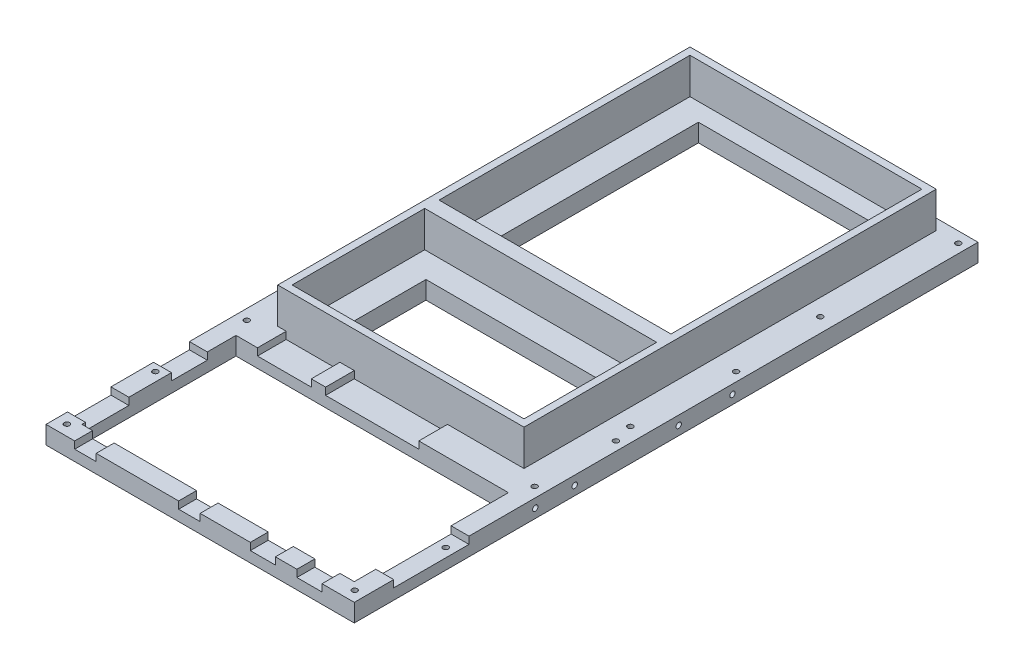
SolidWorks part; units mm, degrees
ref_plane "前视基准面" through (0, 0, 0) normal (0, 0, 1) x (1, 0, 0)
ref_plane "上视基准面" through (0, 0, 0) normal (0, 1, 0) x (1, 0, 0)
ref_plane "右视基准面" through (0, 0, 0) normal (1, 0, 0) x (0, 0, -1)
other "Configuration Table"
sketch "草图1" plane through (0, 0, 0) normal (0, 1, 0) x (1, 0, 0)
  line L1 (-43, -60.5) -> (43, -60.5)
  line L2 (-43, -60.5) -> (-43, 60.5)
  line L3 (-43, 60.5) -> (43, 60.5)
  line L4 (43, -60.5) -> (43, 60.5)
  line L5 (-43, -60.5) -> (43, 60.5) construction
  line L6 (-43, 60.5) -> (43, -60.5) construction
  line L7 (-25, 50.5) -> (25, 50.5)
  line L8 (-25, 50.5) -> (-25, -4.5)
  line L9 (-25, -4.5) -> (25, -4.5)
  line L10 (25, 50.5) -> (25, -4.5)
  line L11 (-25, -25.5) -> (25, -25.5)
  line L12 (-25, -25.5) -> (-25, -50.5)
  line L13 (-25, -50.5) -> (25, -50.5)
  line L14 (25, -25.5) -> (25, -50.5)
  line L15 (-43, -60.5) -> (43, -60.5)
  line L16 (-43, -60.5) -> (-43, -113.5)
  line L17 (-43, -113.5) -> (43, -113.5)
  line L18 (43, -60.5) -> (43, -113.5)
  line L19 (-38, -65.5) -> (38, -65.5)
  line L20 (-38, -65.5) -> (-38, -108.5)
  line L21 (-38, -108.5) -> (38, -108.5)
  line L22 (38, -65.5) -> (38, -108.5)
  point P0 (0, 0)
  dimension "D1" = 86
  dimension "D2" = 121
  dimension "D3" = 10
  dimension "D4" = 18
  dimension "D5" = 18
  dimension "D6" = 55
  dimension "D7" = 10
  dimension "D8" = 25
  dimension "D9" = 5
  dimension "D10" = 5
  dimension "D11" = 5
  dimension "D12" = 5
  dimension "D13" = 53
extrude "凸台-拉伸1" add sketch "草图1" along normal blind 5 contours L18 L1 L16 L17 L19 L22 L21 L20 | L2 L3 L4 L1 | L9 L10 L7 L8 | L11 L14 L13 L12 region at (0, 0, 61.5102)
sketch "草图4" plane through (0, 5, 0) normal (0, 1, 0) x (1, 0, 0)
  line L0 (-43, 60.5) -> (43, 60.5) construction
  line L1 (-34.35, 57.5) -> (34.35, 57.5)
  line L2 (-34.35, 57.5) -> (-34.35, -57.5)
  line L3 (-34.35, -57.5) -> (34.35, -57.5)
  line L4 (34.35, 57.5) -> (34.35, -57.5)
  line L5 (-32.35, -18.5) -> (32.35, -18.5)
  line L6 (-32.35, -18.5) -> (-32.35, -55.5)
  line L7 (-32.35, -55.5) -> (32.35, -55.5)
  line L8 (32.35, -18.5) -> (32.35, -55.5)
  line L9 (32.35, -14.5) -> (-32.35, -14.5)
  line L10 (32.35, -14.5) -> (32.35, 55.5)
  line L11 (32.35, 55.5) -> (-32.35, 55.5)
  line L12 (-32.35, -14.5) -> (-32.35, 55.5)
  line L13 (43, 60.5) -> (43, -113.5) construction
  line L14 (-43, 60.5) -> (-43, -113.5) construction
  dimension "D1" = 5
  dimension "D2" = 10.65
  dimension "D3" = 10.65
  dimension "D4" = 2
  dimension "D5" = 2
  dimension "D6" = 2
  dimension "D7" = 70
  dimension "D8" = 79
  dimension "D9" = 37
  dimension "D10" = 2
extrude "凸台-拉伸2" add sketch "草图4" along normal blind 10 contours L3 L4 L1 L2 | L6 L7 L8 L5 | L12 L11 L10 L9
sketch "草图5" plane through (0, 5, 0) normal (0, 1, 0) x (1, 0, 0)
  line L0 (-43, 60.5) -> (-43, -113.5) construction
  line L1 (43, 60.5) -> (43, -113.5) construction
  line L2 (-43, 60.5) -> (43, 60.5) construction
  line L3 (-43, -85.5) -> (-38, -85.5)
  line L4 (-38, -65.5) -> (-38, -108.5) construction
  line L5 (-23.6333, -57.5) -> (-23.6333, -113.5)
  line L6 (-34.35, -57.5) -> (34.35, -57.5) construction
  line L7 (-43, -113.5) -> (43, -113.5) construction
  line L8 (38, -85.5) -> (43, -85.5)
  line L9 (38, -65.5) -> (38, -108.5) construction
  line L10 (-25, -25.5) -> (-25, -50.5) construction
  line L12 (-34.35, 57.5) -> (34.35, 57.5) construction
  line L13 (-25, -4.5) -> (25, -4.5) construction
  circle A0 centre (-39, 20.5) radius 0.75
  circle A1 centre (39, 20.5) radius 0.75
  circle A2 centre (-39, -32.5) radius 0.75
  circle A3 centre (39, -32.5) radius 0.75
  circle A4 centre (-40.1428, -60.35) radius 0.75
  circle A5 centre (40.1428, -60.35) radius 0.75
  circle A6 centre (-40.1428, -110.5303) radius 0.75
  circle A7 centre (40.1428, -110.5303) radius 0.75
  circle A8 centre (-40.5, 57.5) radius 0.75
  circle A9 centre (-40.5, -38) radius 0.75
  circle A10 centre (-40.5, -85.5) radius 0.75
  circle A11 centre (40.5, 57.5) radius 0.75
  circle A12 centre (40.5, -38) radius 0.75
  circle A13 centre (40.5, -85.5) radius 0.75
  circle A14 centre (-40.5, -4.5) radius 0.75
  circle A15 centre (40.5, -4.5) radius 0.75
  point P40 (-23.6333, -85.5)
  point P52 (-25, -38)
  dimension "D1" = 1.5
  dimension "D2" = 4
  dimension "D3" = 4
  dimension "D4" = 40
  dimension "D5" = 93
extrude "切除-拉伸1" cut sketch "草图5" against normal through all contours A0 | A2 | A4 | A6 | A7 | A5 | A3 | A1 | A8 | A11 | A9 | A12 | A10 | A13 | A14 | A15
sketch "草图7" plane through (0, 5, 0) normal (0, 1, 0) x (1, 0, 0)
  line L0 (42.9928, -57.5) -> (-42.9928, -57.5) construction
  line L1 (-32, -57.5) -> (-17, -57.5)
  line L2 (-32, -57.5) -> (-32, -65.5)
  line L3 (-32, -65.5) -> (-17, -65.5)
  line L4 (-17, -57.5) -> (-17, -65.5)
  line L5 (-43, 60.5) -> (-43, -113.5) construction
  line L6 (-38, -65.5) -> (38, -65.5) construction
  line L8 (-34.35, -57.5) -> (34.35, -57.5) construction
  line L9 (-13, -57.5) -> (13, -57.5)
  line L10 (-13, -57.5) -> (-13, -65.5)
  line L11 (-13, -65.5) -> (13, -65.5)
  line L12 (13, -57.5) -> (13, -65.5)
  line L13 (-38, -65.5) -> (-38, -108.5) construction
  line L14 (-43, -73.5) -> (-38, -73.5)
  line L15 (-43, -73.5) -> (-43, -83.5)
  line L16 (-43, -83.5) -> (-38, -83.5)
  line L17 (-38, -73.5) -> (-38, -83.5)
  line L18 (-43, -113.5) -> (43, -113.5) construction
  line L19 (-43, -95.3803) -> (-38, -95.3803)
  line L20 (-43, -95.3803) -> (-43, -107.5)
  line L21 (-43, -107.5) -> (-38, -107.5)
  line L22 (-38, -95.3803) -> (-38, -107.5)
  line L23 (-42.9928, -113.3803) -> (42.9928, -113.3803) construction
  line L24 (-38, -108.5) -> (38, -108.5) construction
  line L25 (-35, -108.5) -> (-29, -108.5)
  line L26 (-35, -108.5) -> (-35, -113.5)
  line L27 (-35, -113.5) -> (-29, -113.5)
  line L28 (-29, -108.5) -> (-29, -113.5)
  line L29 (43, 60.5) -> (43, -113.5) construction
  line L30 (-6, -108.5) -> (0, -108.5)
  line L31 (-6, -108.5) -> (-6, -113.5)
  line L32 (-6, -113.5) -> (0, -113.5)
  line L33 (0, -108.5) -> (0, -113.5)
  line L34 (14, -108.5) -> (21, -108.5)
  line L35 (14, -108.5) -> (14, -113.5)
  line L36 (14, -113.5) -> (21, -113.5)
  line L37 (21, -108.5) -> (21, -113.5)
  line L38 (27, -108.5) -> (34, -108.5)
  line L39 (27, -108.5) -> (27, -113.5)
  line L40 (27, -113.5) -> (34, -113.5)
  line L41 (34, -108.5) -> (34, -113.5)
  line L42 (43, -81.5) -> (38, -81.5)
  line L43 (43, -81.5) -> (43, -102.5)
  line L44 (43, -102.5) -> (38, -102.5)
  line L45 (38, -81.5) -> (38, -102.5)
  line L46 (38, -65.5) -> (38, -108.5) construction
  dimension "D1" = 11
  dimension "D2" = 26
  dimension "D3" = 30
  dimension "D4" = 56
  dimension "D5" = 16
  dimension "D6" = 26
  dimension "D7" = 6
  dimension "D8" = 18
  dimension "D9" = 8
  dimension "D10" = 14
  dimension "D11" = 37
  dimension "D12" = 43
  dimension "D13" = 57
  dimension "D14" = 64
  dimension "D15" = 70
  dimension "D16" = 77
  dimension "D17" = 11
  dimension "D18" = 32
extrude "切除-拉伸2" cut sketch "草图7" against normal blind 2
sketch "草图8" plane through (-43, 0, 0) normal (-1, 0, 0) x (0, 0, 1)
  line L0 (0, 0) -> (0, 5)
  line L1 (-57.5, 5) -> (57.5, 5) construction
  circle A0 centre (8, 2.5) radius 0.75
  circle A1 centre (23, 2.5) radius 0.75
  circle A2 centre (52, 2.5) radius 0.75
  circle A3 centre (63, 2.5) radius 0.75
  point P12 (0, 0)
  point P13 (0, 2.5)
  dimension "D1" = 1.5
  dimension "D2" = 8
  dimension "D3" = 15
  dimension "D4" = 29
  dimension "D5" = 11
extrude "切除-拉伸3" cut sketch "草图8" against normal blind 2 contours A0 | A1 | A2 | A3
extrude "切除-拉伸4" cut sketch "草图8<3>" along normal blind 2 from surface contours A0 | A1 | A2 | A3 starting at face at (43, 3.25, 59.25)
sketch "草图8<3>" plane through (-43, 0, 0) normal (-1, 0, 0) x (0, 0, 1) same geometry as "草图8"
